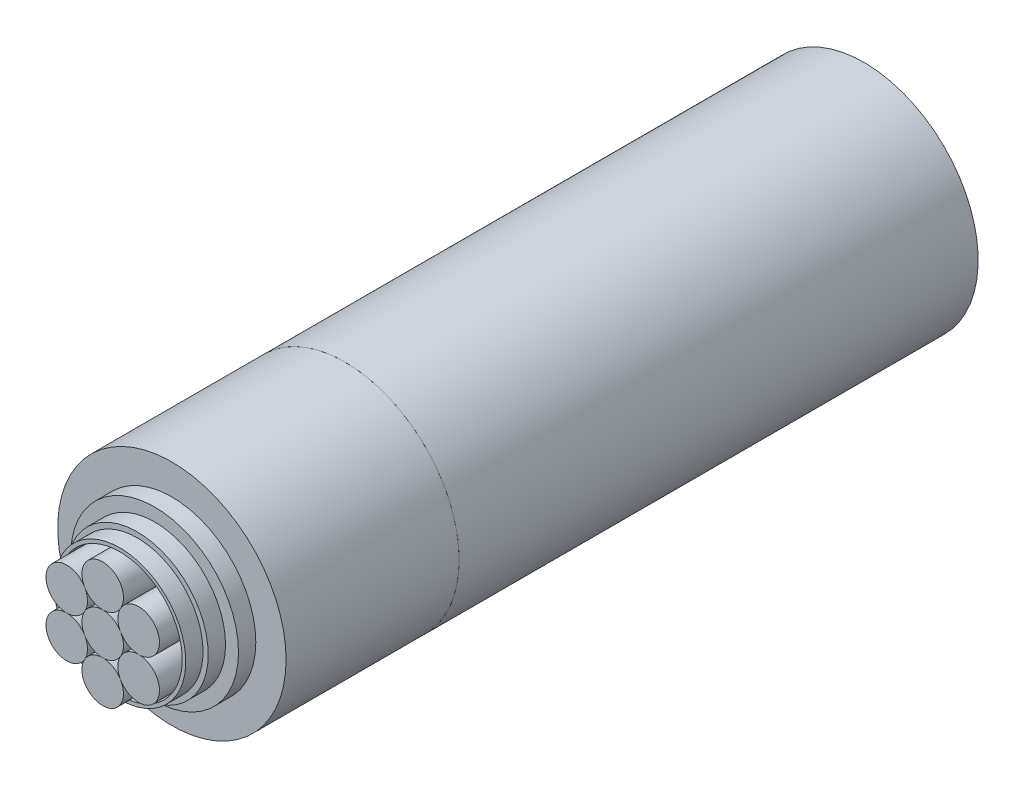
SolidWorks part; units mm, degrees
ref_plane "Ön Düzlem" through (0, 0, 0) normal (0, 0, 1) x (1, 0, 0)
ref_plane "Üst Düzlem" through (0, 0, 0) normal (0, 1, 0) x (1, 0, 0)
ref_plane "Sağ Düzlem" through (0, 0, 0) normal (1, 0, 0) x (0, 0, -1)
sketch "Çizim1" plane through (0, 0, 0) normal (0, 0, 1) x (1, 0, 0)
  circle A0 centre (0, 0) radius 6.6
  circle A1 centre (0, 0) radius 1.2
  circle A2 centre (0, 2.4) radius 1.2
  circle A3 centre (2.0785, 1.2) radius 1.2
  circle A4 centre (2.0785, -1.2) radius 1.2
  circle A5 centre (0, -2.4) radius 1.2
  circle A6 centre (-2.0785, -1.2) radius 1.2
  circle A7 centre (-2.0785, 1.2) radius 1.2
  circle A8 centre (0, 0) radius 3.6
  circle A9 centre (0, 0) radius 3.8
  circle A10 centre (0, 0) radius 4.85
  circle A11 centre (0, 0) radius 4.1
  point P18 (0, 0)
  dimension "D1" = 13.2
  dimension "D2" = 2.4
  dimension "D3" = 2.4
  dimension "D6" = 1.2
  dimension "D7" = 3.6
  dimension "D9" = 0.2
  dimension "D10" = 1.25
  dimension "D11" = 0.3
  dimension "D4" = 2.4
  dimension "D8" = 4.8
  dimension "D5" = 6
extrude "Yükseklik-Ekstrüzyon1" add sketch "Çizim1" along normal blind 10 contours A0 A10 region at (-6.4133, 0, 0)
extrude "Yükseklik-Ekstrüzyon2" add sketch "Çizim1<5>" along normal blind 11 contours A10 A11 region at (-4.7128, 0, 0)
sketch "Çizim1<5>" plane through (0, 0, 0) normal (0, 0, 1) x (1, 0, 0) same geometry as "Çizim1"
extrude "Yükseklik-Ekstrüzyon3" add sketch "Çizim1<6>" along normal blind 12 contours A11 A9 region at (-3.984, 0, 0)
sketch "Çizim1<6>" plane through (0, 0, 0) normal (0, 0, 1) x (1, 0, 0) same geometry as "Çizim1"
extrude "Yükseklik-Ekstrüzyon4" add sketch "Çizim1<7>" along normal blind 13 contours A9 A8 region at (-3.6925, 0, 0)
sketch "Çizim1<7>" plane through (0, 0, 0) normal (0, 0, 1) x (1, 0, 0) same geometry as "Çizim1"
extrude "Yükseklik-Ekstrüzyon5" add sketch "Çizim1<8>" along normal blind 14 separate body contours A7 | A6 | A5 | A4 | A3 | A2 | A1 region at (0, 0, 0) region at (2.0785, 1.2, 0) region at (2.0785, -1.2, 0) region at (0, 2.4, 0) region at (0, -2.4, 0) region at (-2.0785, 1.2, 0) region at (-2.0785, -1.2, 0)
sketch "Çizim1<8>" plane through (0, 0, 0) normal (0, 0, 1) x (1, 0, 0) same geometry as "Çizim1"
scale "Ölçek6" bodies to scale 108 107 106 105 111 109 110 104 scale about origin uniform scaling yes scale factor 0.5
sketch "Çizim3" plane through (0, 0, 0) normal (0, 0, -1) x (-1, 0, 0)
  circle A0 centre (0, 0) radius 3.3
extrude "Yükseklik-Ekstrüzyon8" add sketch "Çizim3" along normal blind 15 separate body
